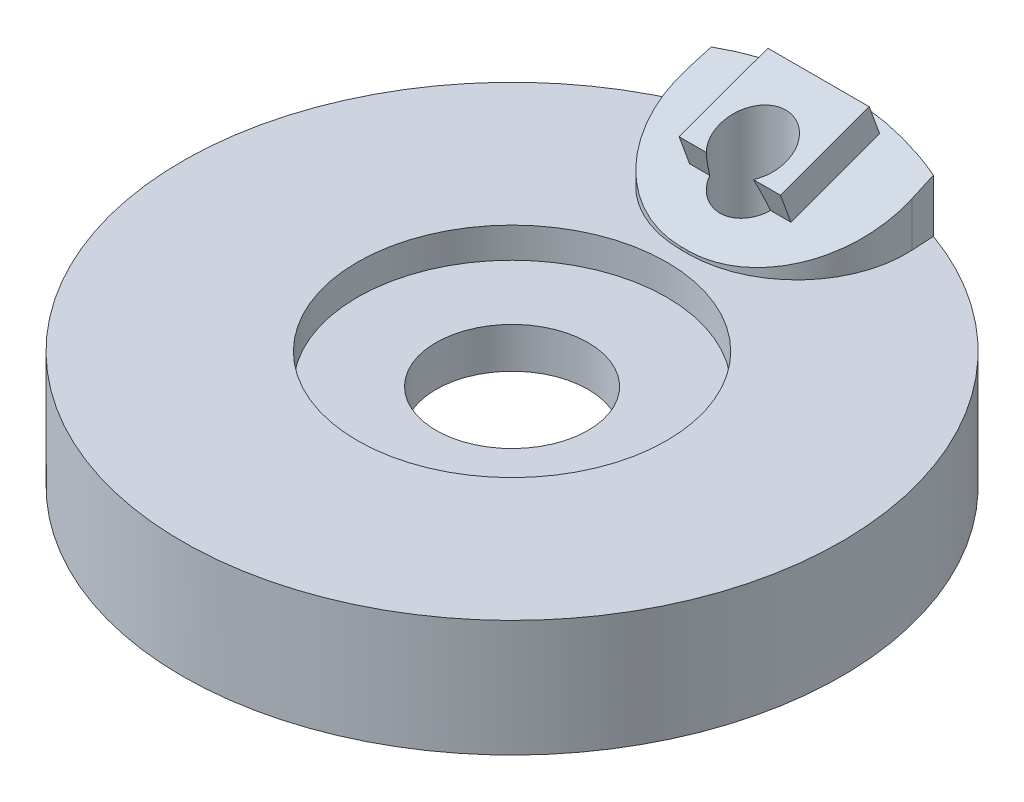
SolidWorks part; units mm, degrees
ref_plane "Front Plane" through (0, 0, 0) normal (0, 0, 1) x (1, 0, 0)
ref_plane "Top Plane" through (0, 0, 0) normal (0, 1, 0) x (1, 0, 0)
ref_plane "Right Plane" through (0, 0, 0) normal (1, 0, 0) x (0, 0, -1)
sketch "Sketch1" plane through (0, 0, 0) normal (0, 1, 0) x (1, 0, 0)
  circle A0 centre (0, 62) radius 13
extrude "Boss-Extrude1" add sketch "Sketch1" along normal blind 4.6 from offset 47.2
sketch "Sketch2" plane through (0, 0, 0) normal (1, 0, 0) x (0, 0, -1)
  line L0 (68.5, 51.8) -> (76.5, 51.8)
  line L1 (76.5, 51.8) -> (76.5, 54.7118)
  line L2 (76.5, 54.7118) -> (68.5, 51.8)
extrude "Boss-Extrude2" add sketch "Sketch2" along normal blind 11 from offset 5.5 offset against normal yes
sketch "Sketch3" plane through (0, 0, 0) normal (1, 0, 0) x (0, 0, -1)
  line L0 (71.0171, 52.6629) -> (74.5171, 53.9368)
  line L1 (74.5171, 53.9368) -> (74.0896, 55.1115)
  line L2 (74.0896, 55.1115) -> (70.5896, 53.8376)
  line L3 (70.5896, 53.8376) -> (71.0171, 52.6629)
extrude "Boss-Extrude3" add sketch "Sketch3" along normal blind 4 from offset 2 offset against normal yes
sketch "Sketch4" plane through (0, 0, 0) normal (0, 1, 0) x (1, 0, 0)
  circle A0 centre (0, 62) radius 25
  circle A1 centre (0, 62) radius 13
extrude "Boss-Extrude4" add sketch "Sketch4" along normal blind 6.2 from offset 51.8 separate body
combine bodies "Combine1" operation type subtract main body 103 bodies to subtract 104
sketch "Sketch5" plane through (0, 0, 0) normal (0, 1, 0) x (1, 0, 0)
  line L0 (-20, 140) -> (20, 140)
  line L1 (20, 140) -> (20, 40)
  line L2 (20, 40) -> (-20, 40)
  line L3 (-20, 40) -> (-20, 140)
  line L4 (-0.141, 68.8) -> (0.141, 68.8)
  line L5 (4.4337, 73.3512) -> (2.3102, 109.6427)
  line L6 (0.3136, 111.5259) -> (-0.3136, 111.5259)
  line L7 (-2.3102, 109.6427) -> (-4.4337, 73.3512)
  arc A0 (-4.4337, 73.3512) -> (-0.141, 68.8) centre (-0.141, 73.1) ccw
  arc A1 (0.141, 68.8) -> (4.4337, 73.3512) centre (0.141, 73.1) ccw
  arc A2 (2.3102, 109.6427) -> (0.3136, 111.5259) centre (0.3136, 109.5259) ccw
  arc A3 (-0.3136, 111.5259) -> (-2.3102, 109.6427) centre (-0.3136, 109.5259) ccw
extrude "Boss-Extrude5" add sketch "Sketch5" along normal blind 6.2 from offset 51.8 separate body
combine bodies "Combine2" operation type subtract main body 105 bodies to subtract 106
sketch "Sketch6" plane through (0, 0, 0) normal (0, 1, 0) x (1, 0, 0)
  line L0 (-5.7983, 72.4652) -> (10.4652, 56.2017)
  line L1 (10.4652, 56.2017) -> (5.7983, 51.5348)
  line L2 (5.7983, 51.5348) -> (-10.4652, 67.7983)
  line L3 (-10.4652, 67.7983) -> (-5.7983, 72.4652)
extrude "Boss-Extrude6" add sketch "Sketch6" along normal blind 2.3 from offset 46.7 separate body
combine bodies "Combine3" operation type subtract main body 107 bodies to subtract 108
sketch "Sketch7" plane through (0, 0, 0) normal (0, 1, 0) x (1, 0, 0)
  line L0 (10.4652, 67.7983) -> (-5.7983, 51.5348)
  line L1 (-5.7983, 51.5348) -> (-10.4652, 56.2017)
  line L2 (-10.4652, 56.2017) -> (5.7983, 72.4652)
  line L3 (5.7983, 72.4652) -> (10.4652, 67.7983)
extrude "Boss-Extrude7" add sketch "Sketch7" along normal blind 2.3 from offset 46.7 separate body
combine bodies "Combine4" operation type subtract main body 109 bodies to subtract 110
sketch "Sketch8" plane through (0, 0, 0) normal (0, 1, 0) x (1, 0, 0)
  circle A0 centre (0, 62) radius 4.6
extrude "Boss-Extrude8" add sketch "Sketch8" along normal blind 2.3 from offset 46.7 separate body
combine bodies "Combine5" operation type subtract main body 111 bodies to subtract 112
sketch "Sketch9" plane through (0, 0, 0) normal (0, 1, 0) x (1, 0, 0)
  circle A0 centre (0, 62) radius 3
extrude "Boss-Extrude9" add sketch "Sketch9" along normal blind 1.8 from offset 48.9 separate body
combine bodies "Combine6" operation type subtract main body 113 bodies to subtract 114
sketch "Sketch10" plane through (0, 0, 0) normal (0, 1, 0) x (1, 0, 0)
  circle A0 centre (0, 62) radius 6.1
extrude "Boss-Extrude10" add sketch "Sketch10" along normal blind 1.7 from offset 50.6 separate body
combine bodies "Combine7" operation type subtract main body 115 bodies to subtract 116
sketch "Sketch11" plane through (0, 0, 0) normal (0, 1, 0) x (1, 0, 0)
  line L0 (5.374, 57.8988) -> (7.7075, 55.5653)
  line L1 (7.7075, 55.5653) -> (6.4347, 54.2925)
  line L2 (6.4347, 54.2925) -> (4.1012, 56.626)
  line L3 (4.1012, 56.626) -> (5.374, 57.8988)
extrude "Boss-Extrude11" add sketch "Sketch11" along normal blind 1.9 from offset 48.9 separate body
combine bodies "Combine8" operation type subtract main body 117 bodies to subtract 118
sketch "Sketch12" plane through (0, 0, 0) normal (0, 1, 0) x (1, 0, 0)
  line L0 (-4.1012, 56.626) -> (-6.4347, 54.2925)
  line L1 (-6.4347, 54.2925) -> (-7.7075, 55.5653)
  line L2 (-7.7075, 55.5653) -> (-5.374, 57.8988)
  line L3 (-5.374, 57.8988) -> (-4.1012, 56.626)
extrude "Boss-Extrude12" add sketch "Sketch12" along normal blind 1.9 from offset 48.9 separate body
combine bodies "Combine9" operation type subtract main body 119 bodies to subtract 120
sketch "Sketch13" plane through (0, 0, 0) normal (0, 1, 0) x (1, 0, 0)
  line L0 (-5.374, 66.1012) -> (-7.7075, 68.4347)
  line L1 (-7.7075, 68.4347) -> (-6.4347, 69.7075)
  line L2 (-6.4347, 69.7075) -> (-4.1012, 67.374)
  line L3 (-4.1012, 67.374) -> (-5.374, 66.1012)
extrude "Boss-Extrude13" add sketch "Sketch13" along normal blind 1.9 from offset 48.9 separate body
combine bodies "Combine10" operation type subtract main body 121 bodies to subtract 122
sketch "Sketch14" plane through (0, 0, 0) normal (0, 1, 0) x (1, 0, 0)
  line L0 (4.1012, 67.374) -> (6.4347, 69.7075)
  line L1 (6.4347, 69.7075) -> (7.7075, 68.4347)
  line L2 (7.7075, 68.4347) -> (5.374, 66.1012)
  line L3 (5.374, 66.1012) -> (4.1012, 67.374)
extrude "Boss-Extrude14" add sketch "Sketch14" along normal blind 1.9 from offset 48.9 separate body
combine bodies "Combine11" operation type subtract main body 123 bodies to subtract 124
sketch "Sketch15" plane through (0, 0, 0) normal (0, 1, 0) x (1, 0, 0)
  circle A0 centre (0, 71.5) radius 2.2
extrude "Boss-Extrude15" add sketch "Sketch15" along normal blind 1.9 from offset 47.1 separate body
combine bodies "Combine12" operation type subtract main body 125 bodies to subtract 126
sketch "Sketch16" plane through (0, 0, 0) normal (0, 1, 0) x (1, 0, 0)
  circle A0 centre (0, 71.5) radius 1.3
extrude "Boss-Extrude16" add sketch "Sketch16" along normal blind 9.1 from offset 48.9 separate body
combine bodies "Combine13" operation type subtract main body 127 bodies to subtract 128
